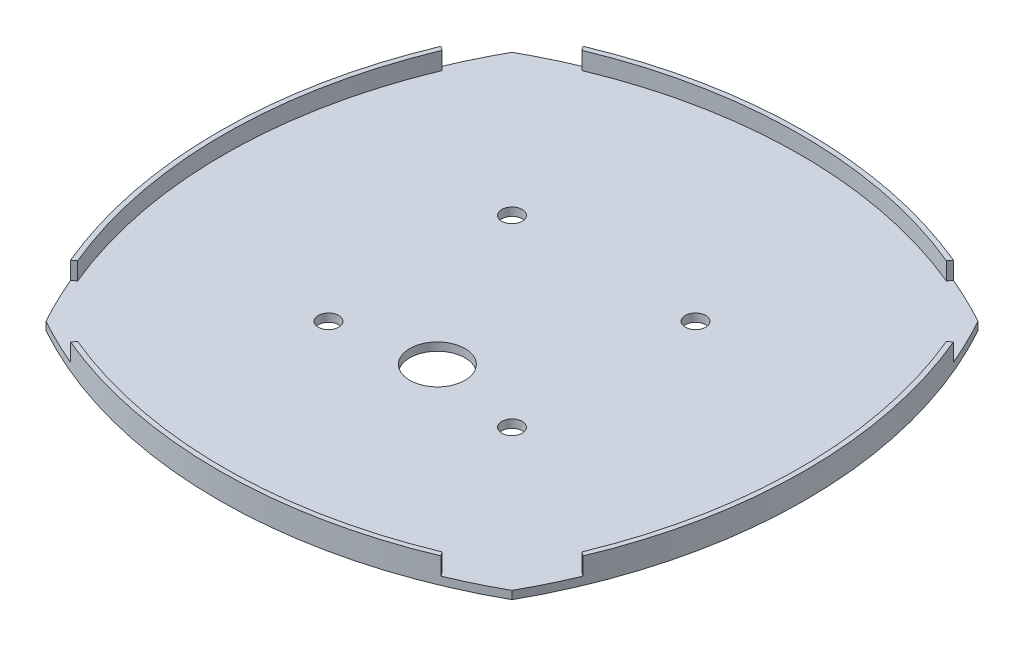
SolidWorks part; units mm, degrees
ref_plane "Front Plane" through (0, 0, 0) normal (0, 0, 1) x (1, 0, 0)
ref_plane "Top Plane" through (0, 0, 0) normal (0, 1, 0) x (1, 0, 0)
ref_plane "Right Plane" through (0, 0, 0) normal (1, 0, 0) x (0, 0, -1)
sketch "Sketch1" plane through (0, 0, 0) normal (0, 1, 0) x (1, 0, 0)
  line L0 (175.429, 389.4302) -> (225.429, 389.4742) construction
  dimension "D1" = 50
sketch "Sketch3" plane through (0, 0, 0) normal (0, 1, 0) x (1, 0, 0)
  line L2 (199.3319, -52.9004) -> (358.0133, -52.9004) construction
  line L3 (199.3319, -52.9004) -> (199.3319, 49.5555) construction
  arc A5 (130.4554, 15.9761) -> (130.4554, -121.7769) centre (256.8431, -52.9004) ccw construction
  arc A6 (268.2084, 15.9761) -> (130.4554, 15.9761) centre (199.3319, -110.4116) ccw construction
  arc A7 (268.2084, -121.7769) -> (268.2084, 15.9761) centre (141.8208, -52.9004) ccw construction
  arc A9 (130.4554, -121.7769) -> (268.2084, -121.7769) centre (199.3319, 4.6107) ccw construction
  arc A12 (271.1535, 18.9212) -> (127.5103, 18.9212) centre (199.3319, -110.4116) ccw
  arc A14 (127.5103, 18.9212) -> (127.5103, -124.722) centre (256.8431, -52.9004) ccw
  arc A15 (127.5103, -124.722) -> (271.1535, -124.722) centre (199.3319, 4.6107) ccw
  arc A16 (271.1535, -124.722) -> (271.1535, 18.9212) centre (141.8208, -52.9004) ccw
  point P0 (199.3319, -52.9004)
  point P15 (199.3319, -52.9004)
  dimension "D1" = 4
extrude "Boss-Extrude1" add sketch "Sketch3" along normal blind 2.5
sketch "Sketch5" plane through (0, 2.5, 0) normal (0, 1, 0) x (1, 0, 0)
  line L0 (141.8208, -52.9004) -> (256.8431, -52.9004) construction
  line L1 (199.3319, 4.6107) -> (199.3319, -110.4116) construction
  line L2 (121.6116, -109.0803) -> (120.3642, -109.9865)
  line L3 (143.1521, -130.6208) -> (142.2458, -131.8681)
  line L4 (277.0523, 3.2794) -> (278.2996, 4.1857)
  line L5 (255.5118, 24.8199) -> (256.418, 26.0673)
  line L6 (277.0523, -109.0803) -> (278.2996, -109.9865)
  line L7 (255.5118, -130.6208) -> (256.418, -131.8681)
  line L8 (121.6125, 3.2817) -> (120.3652, 4.1879)
  line L9 (143.1498, 24.819) -> (142.2436, 26.0663)
  line L10 (110.4063, 20.1528) -> (110.4063, -83.3423) construction
  line L11 (288.2576, 27.2093) -> (288.2576, -79.0531) construction
  line L12 (35.0838, 36.0252) -> (347.5932, 36.0252) construction
  line L13 (32.3242, -141.8261) -> (353.5329, -141.8261) construction
  arc A8 (128.614, -123.6184) -> (270.0499, -123.6184) centre (199.3319, 4.6107) ccw
  arc A9 (270.0499, -123.6184) -> (270.0499, 17.8175) centre (141.8208, -52.9004) ccw
  arc A10 (270.0499, 17.8175) -> (128.614, 17.8175) centre (199.3319, -110.4116) ccw
  arc A11 (128.614, 17.8175) -> (128.614, -123.6184) centre (256.8431, -52.9004) ccw
  arc A12 (143.1521, -130.6208) -> (255.5118, -130.6208) centre (199.3319, 4.6107) ccw
  arc A13 (277.0523, -109.0803) -> (277.0523, 3.2794) centre (141.8208, -52.9004) ccw
  arc A14 (255.5118, 24.8199) -> (143.1498, 24.819) centre (199.3319, -110.4116) ccw
  arc A15 (121.6125, 3.2817) -> (121.6116, -109.0803) centre (256.8431, -52.9004) ccw
  arc A21 (271.1535, 18.9212) -> (127.5103, 18.9212) centre (199.3319, -110.4116) ccw
  arc A22 (271.1535, -124.722) -> (271.1535, 18.9212) centre (141.8208, -52.9004) ccw
  arc A23 (127.5103, -124.722) -> (271.1535, -124.722) centre (199.3319, 4.6107) ccw
  arc A24 (127.5103, 18.9212) -> (127.5103, -124.722) centre (256.8431, -52.9004) ccw
  arc A25 (256.418, 26.0673) -> (142.2436, 26.0663) centre (199.3319, -110.4116) ccw
  arc A26 (278.2996, -109.9865) -> (278.2996, 4.1857) centre (141.8208, -52.9004) ccw
  arc A27 (142.2458, -131.8681) -> (256.418, -131.8681) centre (199.3319, 4.6107) ccw
  arc A28 (120.3652, 4.1879) -> (120.3642, -109.9865) centre (256.8431, -52.9004) ccw
  dimension "D2" = 36
  dimension "D3" = 36
  dimension "D4" = 36
  dimension "D5" = 36
  dimension "D6" = 36
  dimension "D7" = 36
  dimension "D8" = 36
  dimension "D9" = 36
  dimension "D1" = 1.5
  dimension "D10" = 0
extrude "Boss-Extrude2" add sketch "Sketch5" along normal blind 5.4
sketch "Sketch6" plane through (0, 2.5, 0) normal (0, 1, 0) x (1, 0, 0)
  line L0 (127.5103, -124.722) -> (271.1535, 18.9212) construction
  line L1 (127.5103, 18.9212) -> (271.1535, -124.722) construction
  line L2 (199.3319, -54.185) -> (199.3319, 43.8674) construction
  circle A1 centre (199.3319, -84.7202) radius 22.5
  point P12 (199.3319, -52.9004)
  dimension "D1" = 45
ref_plane "Plane1" through (0, 60, 0) normal (0, 1, 0) x (1, 0, 0)
sketch "Sketch11" plane through (0, 2.5, 0) normal (0, 1, 0) x (1, 0, 0)
  line L0 (127.5103, -124.722) -> (271.1535, 18.9212) construction
  line L1 (127.5103, 18.9212) -> (271.1535, -124.722) construction
  line L2 (199.3319, -50.7415) -> (199.3319, 48.5237) construction
  line L3 (199.3319, -52.9004) -> (293.7423, -52.9004) construction
  circle A0 centre (171.0477, -24.6162) radius 3.15
  circle A1 centre (227.6162, -24.6162) radius 3.15
  circle A2 centre (227.6162, -81.1847) radius 3.15
  circle A3 centre (171.0477, -81.1847) radius 3.15
  circle A4 centre (199.3319, -75.9004) radius 8.5
  point P11 (199.3319, -52.9004)
  point P24 (199.3319, -52.9004)
  dimension "D2" = 6.3
  dimension "D4" = 17
  dimension "D3" = 40
  dimension "D5" = 23
  dimension "D1" = 4
extrude "Cut-Extrude2" cut sketch "Sketch11" against normal through all both and the other way through all
sketch "Sketch7" plane through (0, 60, 0) normal (0, 1, 0) x (1, 0, 0)
  line L0 (199.3319, -200054.185) -> (199.3319, 200043.8674) construction
  circle A0 centre (199.3319, -97.9702) radius 9
  dimension "D1" = 18
loft "Loft1" [suppressed] add profiles "Sketch7", "Sketch6"
sketch "Sketch8" [suppressed] plane through (0, 2.5, 0) normal (0, 1, 0) x (1, 0, 0)
  line L0 (199.3319, -97.9702) -> (199.3319, -52.584) construction
  line L1 (127.5103, -124.722) -> (271.1535, 18.9212) construction
  line L2 (127.5103, 18.9212) -> (271.1535, -124.722) construction
  circle A4 centre (199.3319, -97.9702) radius 9 construction
  circle A5 centre (199.3319, -75.9004) radius 9.5
  point P0 (199.3319, -97.9702)
  point P10 (199.3319, -52.9004)
  dimension "D1" = 19
  dimension "D2" = 23
sketch "Sketch9" [suppressed] plane through (0, 60, 0) normal (0, 1, 0) x (1, 0, 0)
  circle A0 centre (199.3319, -97.9702) radius 6
  dimension "D1" = 12
loft "Cut-Loft1" [suppressed] cut profiles "Sketch9", "Sketch8"
